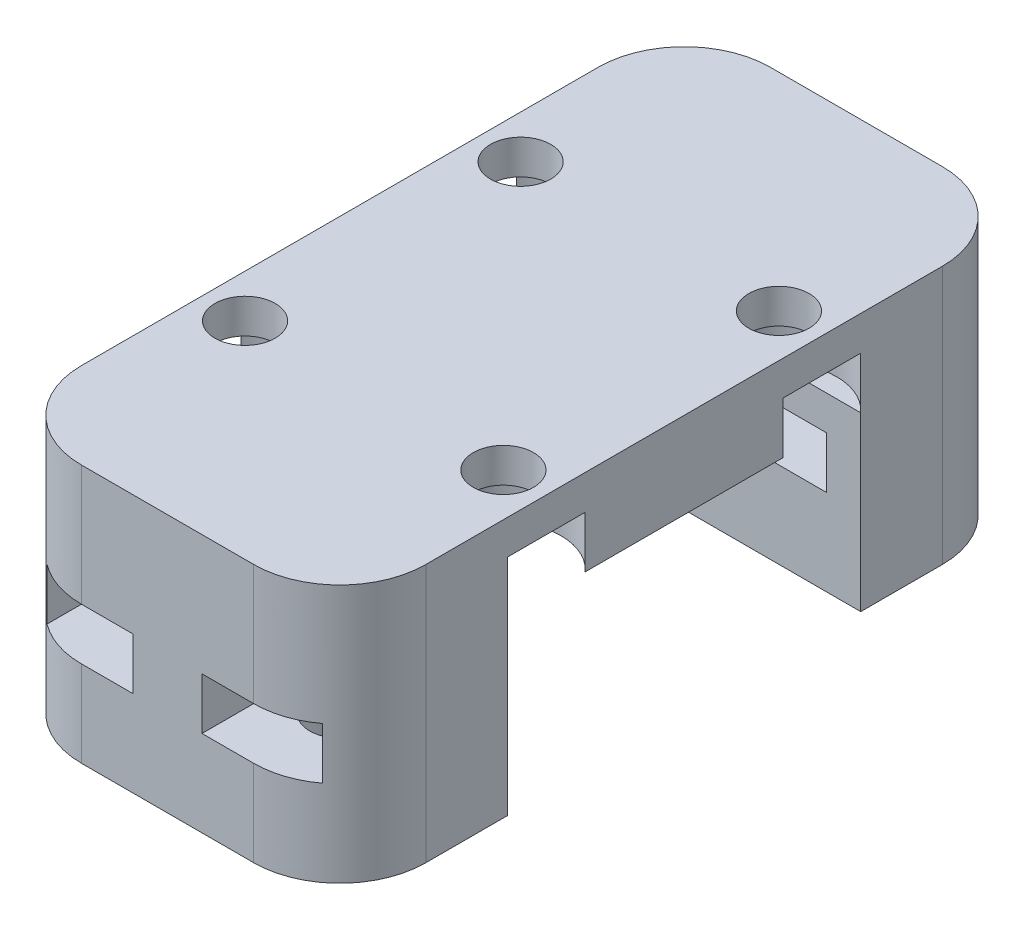
SolidWorks part; units mm, degrees
material "ABS"
ref_plane "Front Plane" through (0, 0, 0) normal (0, 0, 1) x (1, 0, 0)
ref_plane "Top Plane" through (0, 0, 0) normal (0, 1, 0) x (1, 0, 0)
ref_plane "Right Plane" through (0, 0, 0) normal (1, 0, 0) x (0, 0, -1)
sketch "Sketch1" plane through (0, 0, 0) normal (0, 1, 0) x (1, 0, 0)
  line L1 (-10, -20) -> (10, -20)
  line L2 (-10, -20) -> (-10, 20)
  line L3 (-10, 20) -> (10, 20)
  line L4 (10, -20) -> (10, 20)
  line L5 (-10, -20) -> (10, 20) construction
  line L6 (-10, 20) -> (10, -20) construction
  point P0 (0, 0)
  dimension "D1" = 40
  dimension "D2" = 20
extrude "Boss-Extrude1" add sketch "Sketch1" along normal blind 5
sketch "Sketch2" plane through (0, 0, 0) normal (0, -1, 0) x (1, 0, 0)
  line L0 (10, 20) -> (10, -20) construction
  line L1 (-10, 20) -> (10, 20)
  line L2 (-10, 20) -> (-10, 10.25)
  line L3 (-10, 10.25) -> (10, 10.25)
  line L4 (10, 20) -> (10, 10.25)
  line L5 (-10, -20) -> (-10, 20) construction
  line L6 (10, -20) -> (-10, -20)
  line L7 (10, -20) -> (10, -10.25)
  line L8 (10, -10.25) -> (-10, -10.25)
  line L9 (-10, -20) -> (-10, -10.25)
  dimension "D1" = 9.75
  dimension "D2" = 9.75
extrude "Boss-Extrude2" add sketch "Sketch2" along normal blind 10
sketch "Sketch3" plane through (0, 5, 0) normal (0, 1, 0) x (1, 0, 0)
  line L0 (-10, -20) -> (10, -20) construction
  line L1 (-10, 20) -> (-10, -20) construction
  circle A0 centre (-7.5, -8) radius 1.75
  circle A1 centre (-7.5, 8) radius 1.75
  circle A2 centre (7.5, -8) radius 1.75
  circle A3 centre (7.5, 8) radius 1.75
  dimension "D1" = 3.5
  dimension "D4" = 3.5
  dimension "D6" = 3.5
  dimension "D8" = 3.5
  dimension "D2" = 12
  dimension "D3" = 2.5
  dimension "D5" = 16
  dimension "D7" = 15
extrude "Cut-Extrude1" cut sketch "Sketch3" against normal blind 5
sketch "Sketch4" plane through (0, 0, 0) normal (0, -1, 0) x (1, 0, 0)
  circle A13 centre (7.5, 8) radius 3.3634
  circle A14 centre (-7.5, 8) radius 3.3634
  circle A15 centre (-7.5, -8) radius 3.3634
  circle A16 centre (7.5, -8) radius 3.3634
extrude "Cut-Extrude2" cut sketch "Sketch4" against normal blind 3
sketch "Sketch5" plane through (0, -10, 0) normal (0, -1, 0) x (1, 0, 0)
  line L0 (10, -10.25) -> (-10, -10.25) construction
  line L1 (10, -20) -> (10, -10.25) construction
  line L2 (-10, 10.25) -> (10, 10.25) construction
  circle A0 centre (-5, -15) radius 1.75
  circle A1 centre (5, -15) radius 1.75
  circle A2 centre (-5, 15) radius 1.75
  circle A3 centre (5, 15) radius 1.75
  dimension "D1" = 3.5
  dimension "D3" = 3.5
  dimension "D6" = 3.5
  dimension "D7" = 4.75
  dimension "D8" = 3.5
  dimension "D2" = 4.75
  dimension "D4" = 10
  dimension "D5" = 5
extrude "Cut-Extrude3" cut sketch "Sketch5" against normal blind 8
sketch "Sketch6" plane through (0, -2, 0) normal (0, -1, 0) x (1, 0, 0)
  line L13 (-8, -20) -> (-2, -20)
  line L14 (-8, -20) -> (-8, -10)
  line L15 (-8, -10) -> (-2, -10)
  line L16 (-2, -20) -> (-2, -10)
  line L17 (-8, -20) -> (-2, -10) construction
  line L18 (-8, -10) -> (-2, -20) construction
  line L19 (8, -20) -> (2, -20)
  line L20 (8, -20) -> (8, -10)
  line L21 (8, -10) -> (2, -10)
  line L22 (2, -20) -> (2, -10)
  line L23 (8, -20) -> (2, -10) construction
  line L24 (8, -10) -> (2, -20) construction
  line L25 (8, 10) -> (2, 10)
  line L26 (8, 10) -> (8, 20)
  line L27 (8, 20) -> (2, 20)
  line L28 (2, 10) -> (2, 20)
  line L29 (8, 10) -> (2, 20) construction
  line L30 (8, 20) -> (2, 10) construction
  line L35 (-8, 20) -> (-2, 20)
  line L36 (-8, 20) -> (-8, 10)
  line L37 (-8, 10) -> (-2, 10)
  line L38 (-2, 20) -> (-2, 10)
  line L39 (-8, 20) -> (-2, 10) construction
  line L40 (-8, 10) -> (-2, 20) construction
  point P0 (-5, -15)
  point P7 (5, -15)
  point P13 (5, 15)
  point P18 (-5, 15)
  dimension "D1" = 6
  dimension "D2" = 10
  dimension "D3" = 6
  dimension "D4" = 10
  dimension "D6" = 10
extrude "Cut-Extrude4" cut sketch "Sketch6" along normal blind 3
sketch "Sketch7" plane through (0, -2, 0) normal (0, -1, 0) x (1, 0, 0)
  circle A0 centre (-5, -15) radius 1.75
  circle A1 centre (5, -15) radius 1.75
  circle A2 centre (5, 15) radius 1.75
  circle A3 centre (-5, 15) radius 1.75
  dimension "D1" = 3.5
  dimension "D2" = 3.5
  dimension "D3" = 3.5
  dimension "D4" = 3.5
extrude "Cut-Extrude5" cut sketch "Sketch7" against normal blind 3
fillet "Fillet1" radius 5 4 edges at (-10, -2.5, -20) (10, -2.5, -20) (-10, -2.5, 20) (10, -2.5, 20)
sketch "Sketch10" plane through (10, 0, 0) normal (1, 0, 0) x (0, 0, -1)
  line L0 (-15, 5) -> (15, 5) construction
  line L1 (-5.75, 0) -> (5.75, 0)
  line L2 (-5.75, 0) -> (-5.75, 5)
  line L3 (-5.75, 5) -> (5.75, 5)
  line L4 (5.75, 0) -> (5.75, 5)
  line L5 (5.75, 0) -> (5.75, 3) construction
extrude "Cut-Extrude6" [suppressed] cut sketch "Sketch10" against normal blind 2
